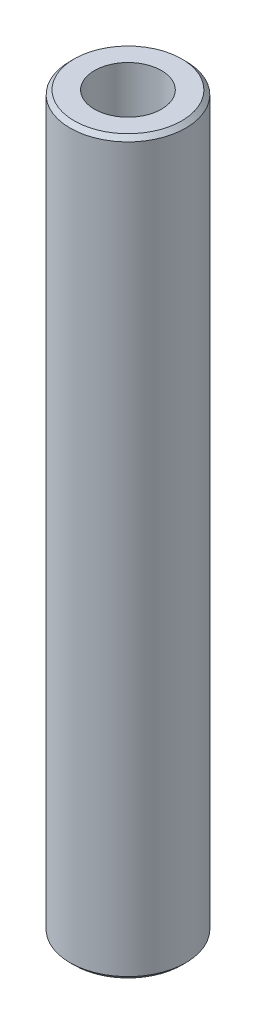
SolidWorks part; units mm, degrees
ref_plane "Front Plane" through (0, 0, 0) normal (0, 0, 1) x (1, 0, 0)
ref_plane "Top Plane" through (0, 0, 0) normal (0, 1, 0) x (1, 0, 0)
ref_plane "Right Plane" through (0, 0, 0) normal (1, 0, 0) x (0, 0, -1)
sketch "Sketch1" plane through (0, 0, 0) normal (0, 1, 0) x (1, 0, 0)
  circle A0 centre (0, 0) radius 47.5
  dimension "SHAFT_OD" = 95
extrude "Boss-Extrude1" add sketch "Sketch1" along normal blind 600
sketch "Sketch2" plane through (0, 0, 0) normal (0, 1, 0) x (1, 0, 0)
  circle A0 centre (0, 0) radius 27.5
  dimension "BORE_D" = 55.0001
extrude "Cut-Extrude1" cut sketch "Sketch2" along normal through all
chamfer "Chamfer1" distance 3.4141 angle 45 2 edges at (0, 600, 47.5) (0, 0, 47.5)
